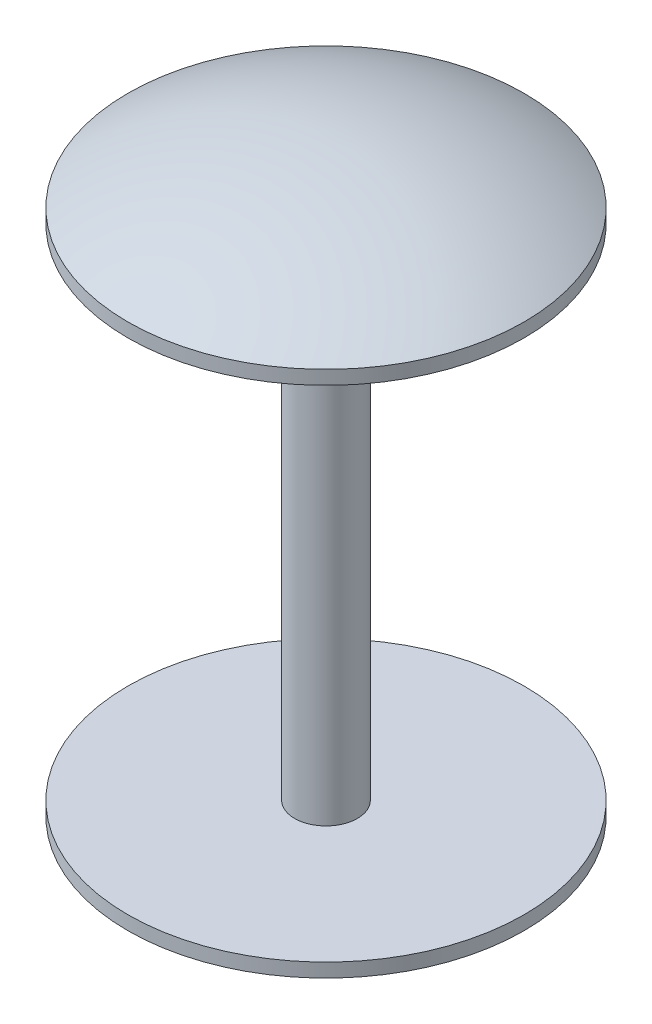
SolidWorks part; units mm, degrees
ref_plane "Front" through (0, 0, 0) normal (0, 0, 1) x (1, 0, 0)
ref_plane "Top" through (0, 0, 0) normal (0, 1, 0) x (1, 0, 0)
ref_plane "Right" through (0, 0, 0) normal (1, 0, 0) x (0, 0, -1)
sketch "Sketch1" plane through (0, 0, 0) normal (0, 1, 0) x (1, 0, 0)
  circle A0 centre (0, 0) radius 2.2616
  circle A1 centre (0, 0) radius 14.2787
  circle A3 centre (0, 0) radius 2.2616 construction
  circle A4 centre (0, 0) radius 14.2787 construction
extrude "Boss-Extrude1" add sketch "Sketch1" along normal mid plane 38 contours A0 | A1 A0 region at (0, 0, 0) region at (-13.8748, 0, 0)
extrude "Cut-Extrude1" cut sketch "Sketch1<3>" along direction (0, 1, 0) on the side against the normal mid plane 36 contours A1 A0 region at (-13.8748, 0, 0)
sketch "Sketch1<3>" plane through (0, 0, 0) normal (0, 1, 0) x (1, 0, 0) same geometry as "Sketch1"
dome "Dome1" faces to dome 1 distance 4 reverse direction no elliptical dome no face at (0, -19, 14.2787) parameters "D1"=4
dome "Dome2" faces to dome 1 distance 4 reverse direction no elliptical dome no face at (0, 19, 14.2787) parameters "D1"=4
